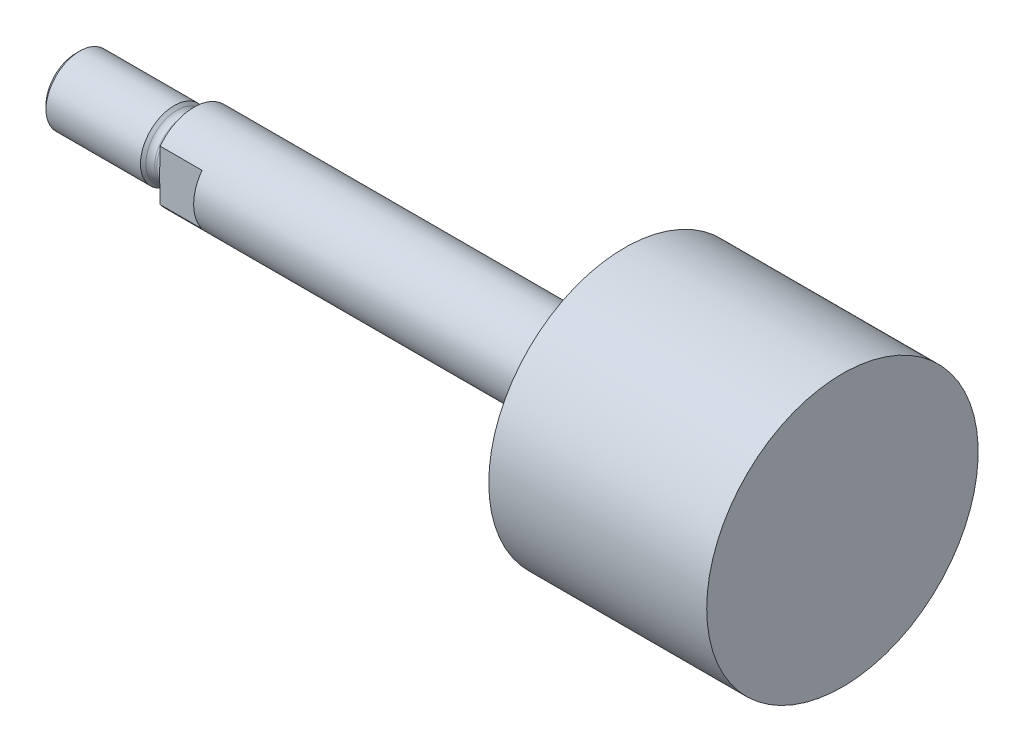
SolidWorks part; units mm, degrees
material "Plain Carbon Steel"
ref_plane "Front Plane" through (0, 0, 0) normal (0, 0, 1) x (1, 0, 0)
ref_plane "Top Plane" through (0, 0, 0) normal (0, 1, 0) x (1, 0, 0)
ref_plane "Right Plane" through (0, 0, 0) normal (1, 0, 0) x (0, 0, -1)
sketch "Sketch1" plane through (0, 0, 0) normal (0, 0, 1) x (1, 0, 0)
  line L0 (-9.525, 0) -> (-9.525, 7.9375)
  line L1 (-9.525, 7.9375) -> (71.4248, 7.9375)
  line L2 (71.4248, 7.9375) -> (71.4248, 25.5206)
  line L3 (71.4248, 25.5206) -> (112.395, 25.5206)
  line L4 (112.395, 25.5206) -> (112.395, 0)
  line L5 (112.395, 0) -> (-9.525, 0)
  line L6 (112.395, 0) -> (-9.525, 0) construction
revolve "Revolve1" add sketch "Sketch1" angle 360 about L6 reverse direction yes
sketch "Sketch2" plane through (0, 0, 0) normal (0, 0, 1) x (1, 0, 0)
  line L0 (-31.75, 0) -> (-31.75, 5.5944)
  line L1 (-31.75, 5.5944) -> (-30.9944, 6.35)
  line L2 (-30.9944, 6.35) -> (-13.2334, 6.35)
  line L3 (-13.2334, 6.35) -> (-12.7264, 5.843)
  line L4 (-11.5589, 5.3594) -> (-11.176, 5.3594)
  line L5 (-9.525, 7.0104) -> (-9.525, 0)
  line L6 (-9.525, 0) -> (-31.75, 0)
  line L7 (-9.525, 0) -> (-31.75, 0) construction
  arc A0 (-12.7264, 5.843) -> (-11.5589, 5.3594) centre (-11.5589, 7.0104) ccw
  arc A1 (-11.176, 5.3594) -> (-9.525, 7.0104) centre (-11.176, 7.0104) ccw
revolve "Revolve2" add sketch "Sketch2" angle 360 about L7 reverse direction yes
cosmetic thread "Cosmetic Thread1" parameters "D1"=18.5166, "D2"=11.1887
ref_plane "Plane1" through (0, 0, 0) normal (1, 0, 0) x (0, 0, -1)
ref_plane "Plane2" through (-9.525, 0, 0) normal (1, 0, 0) x (0, 0, -1)
ref_plane "Plane3" through (-10.16, 0, 0) normal (1, 0, 0) x (0, 0, -1)
sketch "Sketch3" plane through (-10.16, 0, 0) normal (1, 0, 0) x (0, 0, -1)
  line L0 (-15.875, 15.875) -> (-15.875, -15.875)
  line L1 (-15.875, -15.875) -> (15.875, -15.875)
  line L2 (15.875, -15.875) -> (15.875, 15.875)
  line L3 (15.875, 15.875) -> (-15.875, 15.875)
  line L4 (-6.35, 7.9375) -> (-6.35, -7.9375)
  line L5 (-6.35, -7.9375) -> (6.35, -7.9375)
  line L6 (6.35, -7.9375) -> (6.35, 7.9375)
  line L7 (6.35, 7.9375) -> (-6.35, 7.9375)
extrude "Cut-Extrude1" cut sketch "Sketch3" along normal blind 8.509
ref_plane "Plane4" through (193.3448, 0, 0) normal (1, 0, 0) x (0, 0, -1)
ref_plane "Plane5" through (-31.75, 0, 0) normal (1, 0, 0) x (0, 0, -1)
ref_plane "Plane6" through (-9.525, 0, 0) normal (1, 0, 0) x (0, 0, -1)
ref_plane "Plane7" through (-9.525, 0, 0) normal (1, 0, 0) x (0, 0, -1)
ref_plane "Plane8" through (-1.651, 0, 0) normal (1, 0, 0) x (0, 0, -1)
ref_plane "Plane9" through (0, 0, 0) normal (1, 0, 0) x (0, 0, -1)
ref_plane "Plane10" through (0, 0, 0) normal (0, 1, 0) x (1, 0, 0)
ref_plane "Plane11" through (-36.449, 0, 0) normal (1, 0, 0) x (0, 0, -1)
ref_plane "dia1 XY" through (-9.525, 0, 0) normal (1, 0, 0) x (0, 0, -1)
ref_plane "dia1 XZ" through (0, 7.9375, 0) normal (0, -1, 0) x (-1, 0, 0)
ref_plane "dia1 YZ" through (0, 0, 0) normal (0, 0, -1) x (-1, 0, 0)
ref_axis "dia1 X" through (-9.525, 7.9375, 80.9) along (0, 0, -1)
ref_axis "dia1 Y" through (-9.525, -50, 0) along (0, 1, 0)
ref_axis "dia1 Z" through (80.9, 7.9375, 0) along (-1, 0, 0)
sketch3d "dia1"
  point P0 (-9.525, 7.9375, 0)
ref_plane "dia12 XY" through (0, 0, 0) normal (1, 0, 0) x (0, 0, -1)
ref_plane "dia12 XZ" through (0, 0, 0) normal (0, -1, 0) x (-1, 0, 0)
ref_plane "dia12 YZ" through (0, 0, 26.4858) normal (0, 0, -1) x (-1, 0, 0)
ref_axis "dia12 X" through (0, 0, 80.9) along (0, 0, -1)
ref_axis "dia12 Y" through (0, -50, 26.4858) along (0, 1, 0)
ref_axis "dia12 Z" through (80.9, 0, 26.4858) along (-1, 0, 0)
sketch3d "dia12"
  point P0 (0, 0, 26.4858)
ref_plane "dia2 XY" through (-9.525, 0, 0) normal (1, 0, 0) x (0, 0, -1)
ref_plane "dia2 XZ" through (0, -7.9375, 0) normal (0, -1, 0) x (-1, 0, 0)
ref_plane "dia2 YZ" through (0, 0, 0) normal (0, 0, -1) x (-1, 0, 0)
ref_axis "dia2 X" through (-9.525, -7.9375, 80.9) along (0, 0, -1)
ref_axis "dia2 Y" through (-9.525, -50, 0) along (0, 1, 0)
ref_axis "dia2 Z" through (80.9, -7.9375, 0) along (-1, 0, 0)
sketch3d "dia2"
  point P0 (-9.525, -7.9375, 0)
ref_plane "dia22 XY" through (0, 0, 0) normal (1, 0, 0) x (0, 0, -1)
ref_plane "dia22 XZ" through (0, 0, 0) normal (0, -1, 0) x (-1, 0, 0)
ref_plane "dia22 YZ" through (0, 0, -26.4858) normal (0, 0, -1) x (-1, 0, 0)
ref_axis "dia22 X" through (0, 0, 80.9) along (0, 0, -1)
ref_axis "dia22 Y" through (0, -50, -26.4858) along (0, 1, 0)
ref_axis "dia22 Z" through (80.9, 0, -26.4858) along (-1, 0, 0)
sketch3d "dia22"
  point P0 (0, 0, -26.4858)
ref_plane "rl1 XY" through (-31.75, 0, 0) normal (1, 0, 0) x (0, 0, -1)
ref_plane "rl1 XZ" through (0, 0, 0) normal (0, -1, 0) x (-1, 0, 0)
ref_plane "rl1 YZ" through (0, 0, 0) normal (0, 0, -1) x (-1, 0, 0)
ref_axis "rl1 X" through (-31.75, 0, 80.9) along (0, 0, -1)
ref_axis "rl1 Y" through (-31.75, -50, 0) along (0, 1, 0)
ref_axis "rl1 Z" through (80.9, 0, 0) along (-1, 0, 0)
sketch3d "rl1"
  point P0 (-31.75, 0, 0)
ref_plane "rl2 XY" through (-9.525, 0, 0) normal (1, 0, 0) x (0, 0, -1)
ref_plane "rl2 XZ" through (0, 0, 0) normal (0, -1, 0) x (-1, 0, 0)
ref_plane "rl2 YZ" through (0, 0, 0) normal (0, 0, -1) x (-1, 0, 0)
ref_axis "rl2 X" through (-9.525, 0, 80.9) along (0, 0, -1)
ref_axis "rl2 Y" through (-9.525, -50, 0) along (0, 1, 0)
ref_axis "rl2 Z" through (80.9, 0, 0) along (-1, 0, 0)
sketch3d "rl2"
  point P0 (-9.525, 0, 0)
ref_plane "rod_cp XY" through (0, 0, 0) normal (1, 0, 0) x (0, 0, -1)
ref_plane "rod_cp XZ" through (0, 0, 0) normal (0, -1, 0) x (-1, 0, 0)
ref_plane "rod_cp YZ" through (0, 0, 0) normal (0, 0, -1) x (-1, 0, 0)
ref_axis "rod_cp X" through (0, 0, 80.9) along (0, 0, -1)
ref_axis "rod_cp Y" through (0, -50, 0) along (0, 1, 0)
ref_axis "rod_cp Z" through (80.9, 0, 0) along (-1, 0, 0)
sketch3d "rod_cp"
  point P0 (0, 0, 0)
ref_plane "stroke1 XY" through (-9.525, 0, 0) normal (1, 0, 0) x (0, 0, -1)
ref_plane "stroke1 XZ" through (0, 0, 0) normal (0, -1, 0) x (-1, 0, 0)
ref_plane "stroke1 YZ" through (0, 0, 0) normal (0, 0, -1) x (-1, 0, 0)
ref_axis "stroke1 X" through (-9.525, 0, 80.9) along (0, 0, -1)
ref_axis "stroke1 Y" through (-9.525, -50, 0) along (0, 1, 0)
ref_axis "stroke1 Z" through (80.9, 0, 0) along (-1, 0, 0)
sketch3d "stroke1"
  point P0 (-9.525, 0, 0)
ref_plane "thd1 XY" through (-31.75, 0, 0) normal (1, 0, 0) x (0, 0, -1)
ref_plane "thd1 XZ" through (0, 6.35, 0) normal (0, -1, 0) x (-1, 0, 0)
ref_plane "thd1 YZ" through (0, 0, 0) normal (0, 0, -1) x (-1, 0, 0)
ref_axis "thd1 X" through (-31.75, 6.35, 80.9) along (0, 0, -1)
ref_axis "thd1 Y" through (-31.75, -50, 0) along (0, 1, 0)
ref_axis "thd1 Z" through (80.9, 6.35, 0) along (-1, 0, 0)
sketch3d "thd1"
  point P0 (-31.75, 6.35, 0)
ref_plane "thd2 XY" through (-31.75, 0, 0) normal (1, 0, 0) x (0, 0, -1)
ref_plane "thd2 XZ" through (0, -6.35, 0) normal (0, -1, 0) x (-1, 0, 0)
ref_plane "thd2 YZ" through (0, 0, 0) normal (0, 0, -1) x (-1, 0, 0)
ref_axis "thd2 X" through (-31.75, -6.35, 80.9) along (0, 0, -1)
ref_axis "thd2 Y" through (-31.75, -50, 0) along (0, 1, 0)
ref_axis "thd2 Z" through (80.9, -6.35, 0) along (-1, 0, 0)
sketch3d "thd2"
  point P0 (-31.75, -6.35, 0)
ref_plane "to_rod_clevis XY" through (-36.449, 0, 0) normal (1, 0, 0) x (0, 0, -1)
ref_plane "to_rod_clevis XZ" through (0, 0, 0) normal (0, -1, 0) x (-1, 0, 0)
ref_plane "to_rod_clevis YZ" through (0, 0, 0) normal (0, 0, -1) x (-1, 0, 0)
ref_axis "to_rod_clevis X" through (-36.449, 0, 80.9) along (0, 0, -1)
ref_axis "to_rod_clevis Y" through (-36.449, -50, 0) along (0, 1, 0)
ref_axis "to_rod_clevis Z" through (80.9, 0, 0) along (-1, 0, 0)
sketch3d "to_rod_clevis"
  point P0 (-36.449, 0, 0)
ref_plane "wf1 XY" through (-9.525, 0, 0) normal (1, 0, 0) x (0, 0, -1)
ref_plane "wf1 XZ" through (0, 0, 0) normal (0, -1, 0) x (-1, 0, 0)
ref_plane "wf1 YZ" through (0, 0, 0) normal (0, 0, -1) x (-1, 0, 0)
ref_axis "wf1 X" through (-9.525, 0, 80.9) along (0, 0, -1)
ref_axis "wf1 Y" through (-9.525, -50, 0) along (0, 1, 0)
ref_axis "wf1 Z" through (80.9, 0, 0) along (-1, 0, 0)
sketch3d "wf1"
  point P0 (-9.525, 0, 0)
ref_plane "wf2 XY" through (-1.651, 0, 0) normal (1, 0, 0) x (0, 0, -1)
ref_plane "wf2 XZ" through (0, 0, 0) normal (0, -1, 0) x (-1, 0, 0)
ref_plane "wf2 YZ" through (0, 0, 0) normal (0, 0, -1) x (-1, 0, 0)
ref_axis "wf2 X" through (-1.651, 0, 80.9) along (0, 0, -1)
ref_axis "wf2 Y" through (-1.651, -50, 0) along (0, 1, 0)
ref_axis "wf2 Z" through (80.9, 0, 0) along (-1, 0, 0)
sketch3d "wf2"
  point P0 (-1.651, 0, 0)
ref_plane "wfw1 XY" through (0, 0, 0) normal (0, 1, 0) x (1, 0, 0)
ref_plane "wfw1 XZ" through (0, 0, -6.35) normal (0, 0, 1) x (1, 0, 0)
ref_plane "wfw1 YZ" through (-9.525, 0, 0) normal (1, 0, 0) x (0, 0, -1)
ref_axis "wfw1 X" through (-80.9, 0, -6.35) along (1, 0, 0)
ref_axis "wfw1 Y" through (-9.525, 0, 50) along (0, 0, -1)
ref_axis "wfw1 Z" through (-9.525, 50, -6.35) along (0, -1, 0)
sketch3d "wfw1"
  point P0 (-9.525, 0, -6.35)
ref_plane "wfw2 XY" through (0, 0, 0) normal (0, 1, 0) x (1, 0, 0)
ref_plane "wfw2 XZ" through (0, 0, 6.35) normal (0, 0, 1) x (1, 0, 0)
ref_plane "wfw2 YZ" through (-9.525, 0, 0) normal (1, 0, 0) x (0, 0, -1)
ref_axis "wfw2 X" through (-80.9, 0, 6.35) along (1, 0, 0)
ref_axis "wfw2 Y" through (-9.525, 0, 50) along (0, 0, -1)
ref_axis "wfw2 Z" through (-9.525, 50, 6.35) along (0, -1, 0)
sketch3d "wfw2"
  point P0 (-9.525, 0, 6.35)
